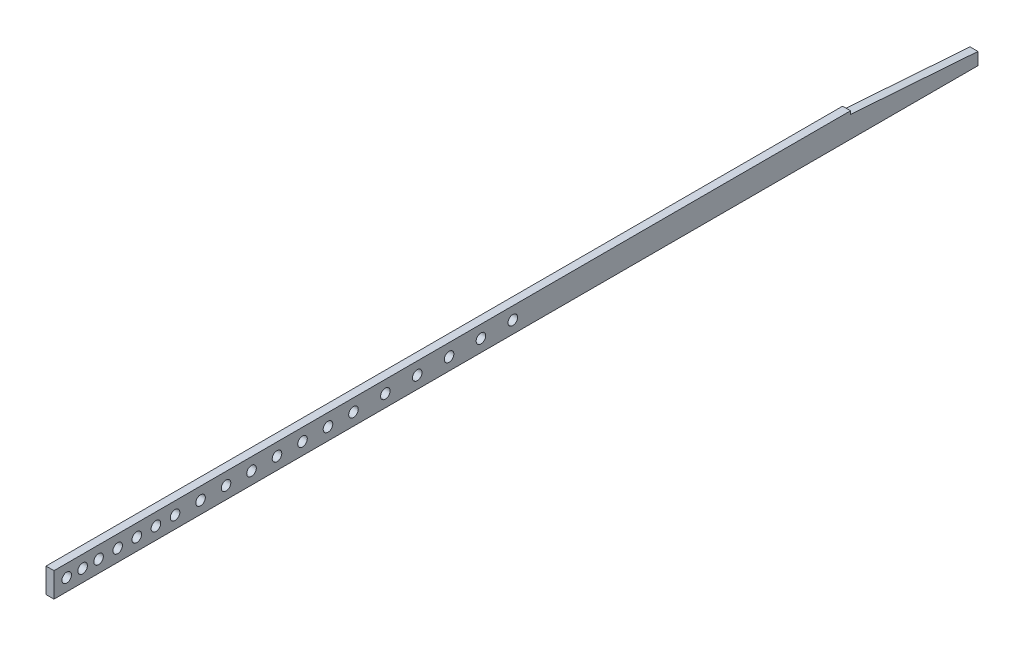
SolidWorks part; units mm, degrees
ref_plane "Ebene vorne" through (0, 0, 0) normal (0, 0, 1) x (1, 0, 0)
ref_plane "Ebene oben" through (0, 0, 0) normal (0, 1, 0) x (1, 0, 0)
ref_plane "Ebene rechts" through (0, 0, 0) normal (1, 0, 0) x (0, 0, -1)
sketch "Skizze1" plane through (0, 0, 0) normal (0, 0, 1) x (1, 0, 0)
  line L1 (0, 0) -> (5, 0)
  line L2 (0, 0) -> (0, 15.5)
  line L3 (0, 15.5) -> (5, 15.5)
  line L4 (5, 0) -> (5, 15.5)
  dimension "D1" = 5
  dimension "D2" = 15.5
extrude "GrundStab" add sketch "Skizze1" along normal blind 580
sketch "Skizze2" plane through (0, 0, 0) normal (-1, 0, 0) x (0, 0, 1)
  line L0 (0, 15.5) -> (0, 7.75)
  line L1 (0, 15.5) -> (0, 0) construction
  line L3 (580, 15.5) -> (0, 15.5) construction
  line L4 (80, 15.5) -> (0, 15.5)
  line L5 (80, 15.5) -> (80, 13.5)
  line L6 (80, 13.5) -> (0, 7.75)
  dimension "D1" = 80
  dimension "D2" = 2
extrude "SchäftungInnen" cut sketch "Skizze2" against normal through all
sketch "Skizze3" [suppressed] plane through (0, 0, 0) normal (-1, 0, 0) x (0, 0, 1)
  line L0 (0, 7.75) -> (-80, 2)
  line L1 (0, 15.5) -> (0, 0) construction
  line L2 (-80, 2) -> (-80, 0)
  line L3 (-80, 0) -> (0, 0)
  line L4 (0, 0) -> (0, 7.75)
  dimension "D1" = 2
  dimension "D2" = 80
extrude "Aufsatz-Linear austragen2" [suppressed] add sketch "Skizze3" against normal through all
sketch "Skizze4" plane through (0, 0, 0) normal (-1, 0, 0) x (0, 0, 1)
  line L0 (580, 7.75) -> (572, 7.75) construction
  line L1 (580, 15.5) -> (580, 0) construction
  circle A0 centre (572, 7.75) radius 3
  circle A1 centre (562, 7.75) radius 3
  circle A2 centre (552, 7.75) radius 3
  circle A3 centre (540, 7.75) radius 3
  circle A4 centre (528, 7.75) radius 3
  circle A5 centre (516, 7.75) radius 3
  circle A6 centre (504, 7.75) radius 3
  circle A7 centre (488, 7.75) radius 3
  circle A8 centre (472, 7.75) radius 3
  circle A9 centre (456, 7.75) radius 3
  circle A10 centre (440, 7.75) radius 3
  circle A11 centre (424, 7.75) radius 3
  circle A12 centre (408, 7.75) radius 3
  circle A13 centre (392, 7.75) radius 3
  circle A14 centre (372, 7.75) radius 3
  circle A15 centre (352, 7.75) radius 3
  circle A16 centre (332, 7.75) radius 3
  circle A17 centre (312, 7.75) radius 3
  circle A18 centre (292, 7.75) radius 3
  dimension "D1" = 6
  dimension "D2" = 8
  dimension "D3" = 3
  dimension "D4" = 5
  dimension "D5" = 8
  dimension "D6" = 6
extrude "Schnitt-Linear austragen1" cut sketch "Skizze4" against normal through all
